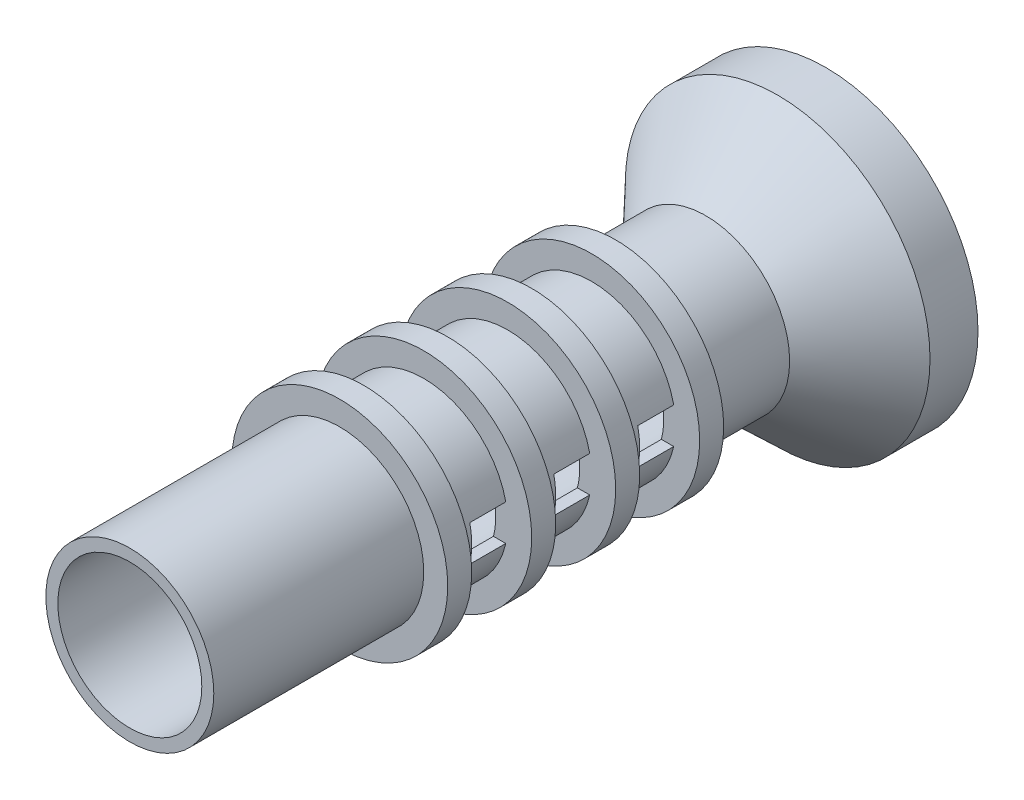
SolidWorks part; units mm, degrees
material "ABS"
ref_plane "正面" through (0, 0, 0) normal (0, 0, 1) x (1, 0, 0)
ref_plane "平面" through (0, 0, 0) normal (0, 1, 0) x (1, 0, 0)
ref_plane "右側面" through (0, 0, 0) normal (1, 0, 0) x (0, 0, -1)
sketch "ｽｹｯﾁ1" plane through (0, 0, 0) normal (0, 0, 1) x (1, 0, 0)
  circle A0 centre (0, 0) radius 3.5 construction
  circle A1 centre (0, 0) radius 6.35
  dimension "D1" = 7
  dimension "D2" = 12.7
ref_plane "平面1" through (0, 0, 5) normal (0, 0, 1) x (1, 0, 0)
sketch "ｽｹｯﾁ2" plane through (0, 0, 5) normal (0, 0, 1) x (1, 0, 0)
  circle A0 centre (0, 0) radius 3.5 construction
  circle A1 centre (0, 0) radius 3.5
ref_plane "平面2" through (0, 0, 29) normal (0, 0, 1) x (1, 0, 0)
ref_plane "平面3" through (0, 0, 24) normal (0, 0, 1) x (1, 0, 0)
sketch "ｽｹｯﾁ5" plane through (0, 0, 29) normal (0, 0, 1) x (1, 0, 0)
  circle A0 centre (0, 0) radius 6.35 construction
  circle A1 centre (0, 0) radius 6.35 construction
  circle A2 centre (0, 0) radius 3.5
  dimension "D1" = 7
extrude "ﾎﾞｽ - 押し出し3" add sketch "ｽｹｯﾁ2" along normal up to surface (19 mm away) contours A1 up to plane "平面3"
extrude "ﾎﾞｽ - 押し出し4" add sketch "ｽｹｯﾁ1" along normal blind 2 separate body
extrude "ﾎﾞｽ - 押し出し5" add sketch "ｽｹｯﾁ5" against normal blind 2
loft "ﾛﾌﾄ1" add section face at (6.35, 0, 2) section face at (3.5, 0, 5) connector at (-0.1759, 6.3476, 2) connector at (-0.0742, 3.4992, 5)
loft "ﾛﾌﾄ2" add section face at (3.5, 0, 24) section face at (3.5, 0, 27) connector at (-0.0749, 3.4992, 24) connector at (-0.0751, 3.4992, 27)
ref_plane "平面5" through (0, 0, 14.5) normal (0, 0, 1) x (1, 0, 0)
ref_plane "平面6" through (0, 0, 15.75) normal (0, 0, 1) x (1, 0, 0)
sketch "ｽｹｯﾁ9" plane through (0, 0, 15.75) normal (0, 0, 1) x (1, 0, 0)
  circle A0 centre (0, 0) radius 4.5
  dimension "D1" = 9
extrude "ﾎﾞｽ - 押し出し6" add sketch "ｽｹｯﾁ9" along normal blind 1
ref_plane "平面7" through (0, 0, 19.25) normal (0, 0, 1) x (1, 0, 0)
sketch "ｽｹｯﾁ10" plane through (0, 0, 19.25) normal (0, 0, 1) x (1, 0, 0)
  circle A1 centre (0, 0) radius 4.5
  circle A2 centre (0, 0) radius 4.5
  dimension "D1" = 0
extrude "ﾎﾞｽ - 押し出し7" add sketch "ｽｹｯﾁ10" along normal blind 1
mirror "ﾐﾗｰ3" about plane through (0, 0, 14.5) normal (0, 0, 1) of "ﾎﾞｽ - 押し出し7", "ﾎﾞｽ - 押し出し6"
sketch "ｽｹｯﾁ6" plane through (0, 0, 0) normal (0, 0, -1) x (-1, 0, 0)
  circle A0 centre (0, 0) radius 2.9
  dimension "D1" = 5.8
extrude "ｶｯﾄ - 押し出し1" cut sketch "ｽｹｯﾁ6" against normal blind 3
sketch "ｽｹｯﾁ7" plane through (0, 0, 3) normal (0, 0, -1) x (-1, 0, 0)
  circle A0 centre (0, 0) radius 1.8
  dimension "D1" = 3.6
extrude "ｶｯﾄ - 押し出し2" cut sketch "ｽｹｯﾁ7" against normal through all
sketch "ｽｹｯﾁ8" plane through (0, 0, 29) normal (0, 0, 1) x (1, 0, 0)
  circle A0 centre (0, 0) radius 3
  dimension "D1" = 6
extrude "ｶｯﾄ - 押し出し3" cut sketch "ｽｹｯﾁ8" against normal offset from surface (23 mm away) 3 up to face at (-1.8, 0, 3)
ref_plane "平面9" through (3.5, 0, 0) normal (1, 0, 0) x (0, 0, -1)
sketch "ｽｹｯﾁ11" plane through (3.5, 0, 0) normal (1, 0, 0) x (0, 0, -1)
  line L0 (0, 0) -> (-29, 0) construction
  line L1 (-29, 6.9851) -> (-29, -6.9851) construction
  line L2 (-16.75, 3.5) -> (-16.75, -3.5) construction
  line L3 (-18.25, 0.75) -> (-16.75, 0.75)
  line L4 (-18.25, 0.75) -> (-18.25, -0.75)
  line L5 (-18.25, -0.75) -> (-16.75, -0.75)
  line L6 (-16.75, 0.75) -> (-16.75, -0.75)
  line L7 (-18.25, 0.75) -> (-16.75, -0.75) construction
  line L8 (-18.25, -0.75) -> (-16.75, 0.75) construction
  line L9 (-13.25, 4.5) -> (-13.25, -4.5) construction
  line L10 (-14.75, 0.75) -> (-13.25, 0.75)
  line L11 (-14.75, 0.75) -> (-14.75, -0.75)
  line L12 (-14.75, -0.75) -> (-13.25, -0.75)
  line L13 (-13.25, 0.75) -> (-13.25, -0.75)
  line L14 (-14.75, 0.75) -> (-13.25, -0.75) construction
  line L15 (-14.75, -0.75) -> (-13.25, 0.75) construction
  line L16 (-9.75, 3.5) -> (-9.75, -3.5) construction
  line L17 (-11.25, 0.75) -> (-9.75, 0.75)
  line L18 (-11.25, 0.75) -> (-11.25, -0.75)
  line L19 (-11.25, -0.75) -> (-9.75, -0.75)
  line L20 (-9.75, 0.75) -> (-9.75, -0.75)
  line L21 (-11.25, 0.75) -> (-9.75, -0.75) construction
  line L22 (-11.25, -0.75) -> (-9.75, 0.75) construction
  point P5 (-17.5, 0)
  point P12 (-14, 0)
  point P19 (-10.5, 0)
  dimension "D1" = 1.5
  dimension "D2" = 1.5
extrude "ｶｯﾄ - 押し出し4" cut sketch "ｽｹｯﾁ11" against normal up to next
